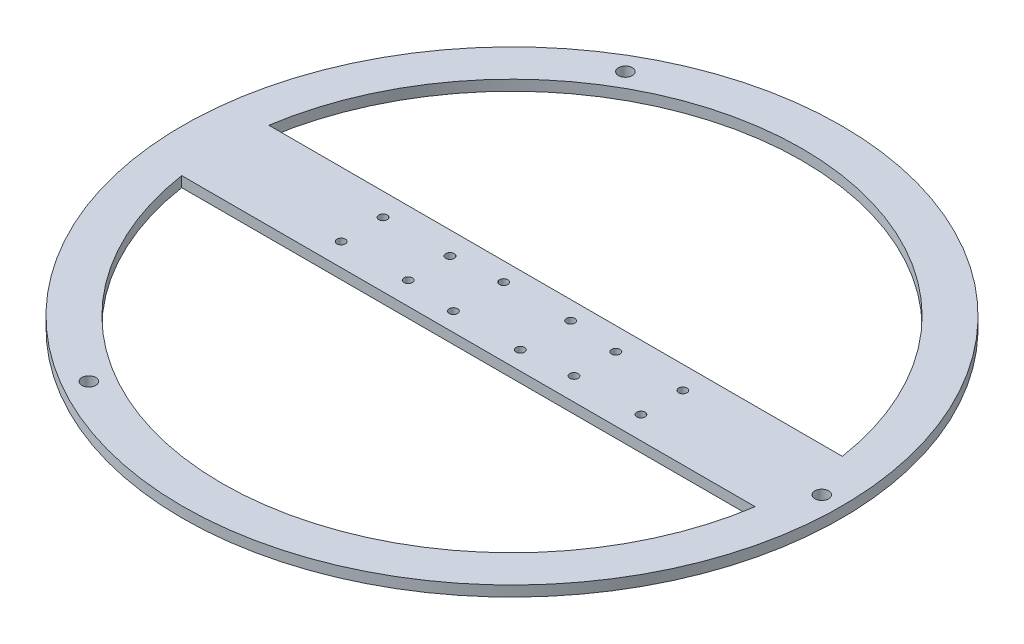
SolidWorks part; units mm, degrees
ref_plane "Front Plane" through (0, 0, 0) normal (0, 0, 1) x (1, 0, 0)
ref_plane "Top Plane" through (0, 0, 0) normal (0, 1, 0) x (1, 0, 0)
ref_plane "Right Plane" through (0, 0, 0) normal (1, 0, 0) x (0, 0, -1)
sketch "Sketch1" plane through (0, 0, 0) normal (0, 1, 0) x (1, 0, 0)
  line L0 (0, 100) -> (0, 0) construction
  line L1 (0, 0) -> (50, 86.6025) construction
  line L2 (-100, 0) -> (100, 0) construction
  line L3 (-10.16, 7.62) -> (10.16, 7.62) construction
  line L4 (-10.16, 7.62) -> (-10.16, -7.62) construction
  line L5 (-10.16, -7.62) -> (10.16, -7.62) construction
  line L6 (10.16, 7.62) -> (10.16, -7.62) construction
  line L7 (-10.16, 7.62) -> (10.16, -7.62) construction
  line L8 (-10.16, -7.62) -> (10.16, 7.62) construction
  line L9 (-25.16, -6.35) -> (-45.48, 6.35) construction
  line L10 (25.16, 6.35) -> (45.48, 6.35) construction
  line L11 (25.16, 6.35) -> (25.16, -6.35) construction
  line L12 (25.16, -6.35) -> (45.48, -6.35) construction
  line L13 (45.48, 6.35) -> (45.48, -6.35) construction
  line L14 (25.16, 6.35) -> (45.48, -6.35) construction
  line L15 (25.16, -6.35) -> (45.48, 6.35) construction
  line L16 (-25.16, 6.35) -> (-45.48, -6.35) construction
  line L17 (-45.48, 6.35) -> (-45.48, -6.35) construction
  line L18 (-25.16, -6.35) -> (-45.48, -6.35) construction
  line L19 (-25.16, 6.35) -> (-25.16, -6.35) construction
  line L20 (-25.16, 6.35) -> (-45.48, 6.35) construction
  line L21 (0, 0) -> (100, 0) construction
  line L22 (0, 0) -> (50, -86.6025) construction
  line L23 (-87, 13.2288) -> (87, 13.2288)
  line L24 (-87, -13.2288) -> (87, -13.2288)
  circle A0 centre (0, 0) radius 100
  circle A12 centre (-10.16, 7.62) radius 1.27
  circle A13 centre (-10.16, -7.62) radius 1.27
  circle A14 centre (10.16, -7.62) radius 1.27
  circle A15 centre (10.16, 7.62) radius 1.27
  circle A16 centre (25.16, 6.35) radius 1.27
  circle A17 centre (25.16, -6.35) radius 1.27
  circle A18 centre (45.48, -6.35) radius 1.27
  circle A19 centre (45.48, 6.35) radius 1.27
  circle A20 centre (-45.48, 6.35) radius 1.27
  circle A21 centre (-45.48, -6.35) radius 1.27
  circle A22 centre (-25.16, -6.35) radius 1.27
  circle A23 centre (-25.16, 6.35) radius 1.27
  circle A24 centre (94, 0) radius 2.1
  arc A31 (87, 13.2288) -> (-87, 13.2288) centre (0, 0) ccw
  circle A32 centre (-47, -81.4064) radius 2.1
  arc A33 (87, -13.2288) -> (-87, -13.2288) centre (0, 0) cw
  circle A34 centre (-47, 81.4064) radius 2.1
  point P18 (0, 0)
  point P27 (35.32, 0)
  point P44 (-35.32, 0)
  dimension "D1" = 200
  dimension "D3" = 60
  dimension "D6" = 2.54
  dimension "D13" = 4.2
  dimension "D16" = 88
  dimension "D2" = 20.32
  dimension "D4" = 60
  dimension "D5" = 15.24
  dimension "D7" = 12.7
  dimension "D8" = 20.32
  dimension "D9" = 15
  dimension "D10" = 174
  dimension "D11" = 3
  dimension "D12" = 0
  dimension "D14" = 6
  dimension "D15" = 13.2288
extrude "Boss-Extrude1" add sketch "Sketch1" along normal blind 3.175
